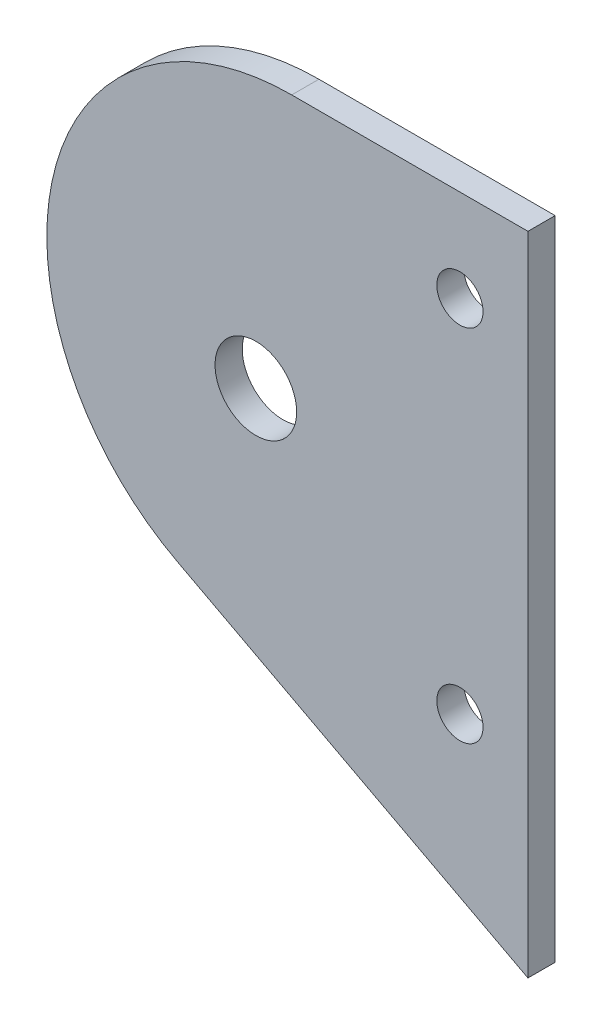
SolidWorks part; units mm, degrees
ref_plane "Plan de face" through (0, 0, 0) normal (0, 0, 1) x (1, 0, 0)
ref_plane "Plan de dessus" through (0, 0, 0) normal (0, 1, 0) x (1, 0, 0)
ref_plane "Plan de droite" through (0, 0, 0) normal (1, 0, 0) x (0, 0, -1)
sketch "Esquisse1" plane through (0, 0, 0) normal (0, 0, 1) x (1, 0, 0)
  line L0 (0, 0) -> (0, 122.747) construction
  line L1 (-175, -20) -> (175, -20) construction
  line L2 (-175, -20) -> (-175, 20) construction
  line L3 (-175, 20) -> (175, 20) construction
  line L4 (175, -20) -> (175, 20) construction
  line L5 (-175, -20) -> (175, 20) construction
  line L6 (-175, 20) -> (175, -20) construction
  line L7 (-1220, 0) -> (-110, 0) construction
  line L8 (-244.959, 40) -> (-110, 40)
  line L9 (110, 40) -> (244.959, 40)
  line L10 (110, 0) -> (110, -20) construction
  line L11 (110, -20) -> (-110, -20) construction
  line L12 (-110, 0) -> (-110, -20) construction
  line L13 (110, 0) -> (-110, -20) construction
  line L14 (110, -20) -> (-110, 0) construction
  line L15 (-244.959, 40) -> (-112.4795, -30)
  line L16 (-112.4795, -30) -> (112.4795, -30)
  line L17 (244.959, 40) -> (112.4795, -30)
  line L18 (-175, 20) -> (-58.3333, 20) construction
  line L19 (-58.3333, 20) -> (58.3333, 20) construction
  line L20 (58.3333, 20) -> (175, 20) construction
  line L21 (110, 0) -> (193.5165, 0) construction
  line L22 (110, 95) -> (-110, 95) construction
  line L23 (110, 95) -> (110, 40) construction
  line L24 (-110, 40) -> (110, 40)
  line L25 (-110, 95) -> (-110, 40) construction
  line L26 (110, 95) -> (-110, 0) construction
  line L27 (110, 0) -> (-110, 95) construction
  circle A0 centre (-175, 20) radius 3
  circle A1 centre (-110, -20) radius 3
  circle A2 centre (110, -20) radius 3
  circle A3 centre (175, 20) radius 3
  circle A4 centre (0, -20) radius 3
  circle A5 centre (-58.3333, 20) radius 3
  circle A6 centre (58.3333, 20) radius 3
  circle A7 centre (0, 78.03) radius 3 construction
  point P0 (0, 0)
  point P8 (0, -10)
  point P20 (0, 47.5)
  point P21 (0, -30)
  point P31 (0, 47.5)
  dimension "D8" = 6
  dimension "D10" = 58.03
  dimension "D1" = 350
  dimension "D2" = 40
  dimension "D3" = 220
  dimension "D4" = 20
  dimension "D5" = 15
  dimension "D6" = 10
  dimension "D7" = 10
  dimension "D9" = 55
extrude "Boss.-Extru.1" add sketch "Esquisse1" along normal blind 2
fillet "Congé1" radius 18 2 edges at (-244.959, 40, 1) (244.959, 40, 1)
fillet "Congé2" radius 20 2 edges at (-112.4795, -30, 1) (112.4795, -30, 1)
sketch "Esquisse2" plane through (0, 0, 0) normal (0, 0, 1) x (1, 0, 0)
  line L1 (201.7182, 61.1482) -> (-155, 61.1482)
  line L2 (201.7182, 61.1482) -> (201.7182, -35.6578)
  line L3 (201.7182, -35.6578) -> (-155, -35.6578)
  line L4 (-155, 61.1482) -> (-155, -35.6578)
  circle A0 centre (-175, 20) radius 3 construction
  dimension "D1" = 20
extrude "Enlèv. mat.-Extru.2" cut sketch "Esquisse2" against normal blind 10 and the other way through all
hole_wizard "Dégagement M31" positions "Esquisse4" profile "Esquisse3" hole size "M3" standard "Ansi Metric" end condition through all
sketch "Esquisse4" plane through (0, 0, 0) normal (0, 0, -1) x (-1, 0, 0)
  line L0 (160, 33.2288) -> (160, 6.7712)
  line L1 (160, 6.7712) -> (175, 10)
  line L2 (175, 20) -> (175, 10)
  circle A3 centre (175, 20) radius 10
  circle A4 centre (175, 20) radius 3 construction
  circle A5 centre (175, 20) radius 20
  point P0 (160, 33.2288)
  point P2 (160, 6.7712)
  dimension "D1" = 20
  dimension "D2" = 40
  dimension "D3" = 15
sketch "Esquisse3" plane through (-160, 33.2288, 0) normal (1, 0, 0) x (0, 1, 0)
  line L0 (0, 0) -> (0, 2)
  line L1 (0, 2) -> (1.7, 2)
  line L2 (1.7, 2) -> (1.7, 0)
  line L5 (1.7, 0) -> (0, 0)
  line L11 (0, -6.35) -> (0, 107.95) construction
  dimension "Diamètre du perçage jusqu'au prochain" = 3.4
  dimension "Profondeur du perçage jusqu'au prochain" = 2
